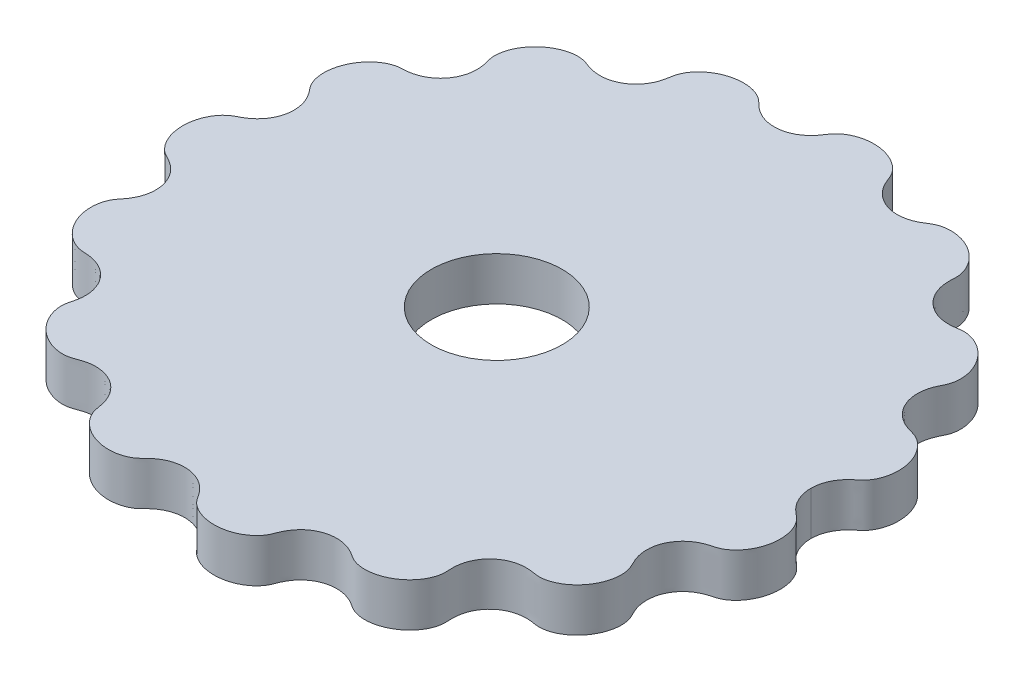
SolidWorks part; units mm, degrees
ref_plane "Front Plane" through (0, 0, 0) normal (0, 0, 1) x (1, 0, 0)
ref_plane "Top Plane" through (0, 0, 0) normal (0, 1, 0) x (1, 0, 0)
ref_plane "Right Plane" through (0, 0, 0) normal (1, 0, 0) x (0, 0, -1)
sketch "Sketch1" plane through (0, 0, 0) normal (0, 1, 0) x (1, 0, 0)
  circle A0 centre (0, 0) radius 50.8 construction
  circle A1 centre (50.8, 0) radius 5.08
  circle A2 centre (46.9331, -19.4403) radius 5.08
  circle A3 centre (35.921, -35.921) radius 5.08
  circle A4 centre (19.4403, -46.9331) radius 5.08
  circle A5 centre (0, -50.8) radius 5.08
  circle A6 centre (-19.4403, -46.9331) radius 5.08
  circle A7 centre (-35.921, -35.921) radius 5.08
  circle A8 centre (-46.9331, -19.4403) radius 5.08
  circle A9 centre (-50.8, 0) radius 5.08
  circle A10 centre (-46.9331, 19.4403) radius 5.08
  circle A11 centre (-35.921, 35.921) radius 5.08
  circle A12 centre (-19.4403, 46.9331) radius 5.08
  circle A13 centre (0, 50.8) radius 5.08
  circle A14 centre (19.4403, 46.9331) radius 5.08
  circle A15 centre (35.921, 35.921) radius 5.08
  circle A16 centre (46.9331, 19.4403) radius 5.08
  point P5 (0, 0)
  point P38 (0, 0)
  dimension "D2" = 10.16
  dimension "D3" = 101.6
  dimension "D1" = 16
sketch "Sketch7" plane through (0, 0, 0) normal (0, 1, 0) x (1, 0, 0)
  line L0 (45.72, 0) -> (-45.72, 0) construction
  circle A0 centre (0, 0) radius 9.525
  spline S0 degree 4 poles (41.7828, 21.3416) (41.6877, 21.0354) (41.5541, 20.4589) (41.4817, 19.5946) (41.6319, 18.466) (41.9776, 17.4811) (42.4848, 16.6203) (43.1091, 15.902) (43.7743, 15.3578) (44.4718, 14.9491) (45.1642, 14.6592) (45.8268, 14.4665) (46.5456, 14.2893) (47.2514, 13.9249) (47.9146, 13.4096) (48.5159, 12.7518) (49.1405, 11.8267) (49.6007, 10.7687) (49.8728, 9.6056) (49.9193, 8.478) (49.8408, 7.6516) (49.6901, 6.9642) (49.5102, 6.4154) (49.2842, 5.9083) (49.0159, 5.4485) (48.7039, 5.0361) (48.3472, 4.6843) (47.9659, 4.386) (47.6077, 4.0839) (47.2427, 3.7363) (46.8855, 3.332) (46.5599, 2.8811) (46.3097, 2.4416) (46.1346, 2.0602) (46.0214, 1.7622) (45.9477, 1.5375) (45.8879, 1.3243) (45.8399, 1.1244) (45.7998, 0.9214) (45.7677, 0.7202) (45.7435, 0.5098) (45.7274, 0.3215) (45.7201, 0.093) (45.7193, -0.0301) (45.7237, -0.2191) (45.7347, -0.4227) (45.7566, -0.6387) (45.8027, -0.9544) (45.8678, -1.2569) (45.9509, -1.5555) (46.0513, -1.8439) (46.1426, -2.0726) (46.2448, -2.2971) (46.3576, -2.5177) (46.4921, -2.7533) (46.6515, -3.0019) (46.8889, -3.3295) (47.1748, -3.6638) (47.4944, -3.9813) (47.8426, -4.2835) (48.1438, -4.5247) (48.4598, -4.7892) (48.7604, -5.1083) (49.0364, -5.4828) (49.2825, -5.909) (49.5155, -6.4255) (49.714, -7.0358) (49.8644, -7.7856) (49.9209, -8.6713) (49.8533, -9.5885) (49.6516, -10.518) (49.3412, -11.3668) (48.9446, -12.1262) (48.4522, -12.8268) (47.8657, -13.4526) (47.2676, -13.9089) (46.6958, -14.2089) (46.1258, -14.398) (45.5852, -14.5294) (44.9666, -14.7315) (44.2565, -15.0606) (43.5536, -15.5189) (42.899, -16.1145) (42.3292, -16.8533) (41.8937, -17.6927) (41.6203, -18.5741) (41.5051, -19.4792) (41.5386, -20.2622) (41.6529, -20.9023) (41.8006, -21.4183) (41.9452, -21.814) (42.1035, -22.1727) (42.2646, -22.4973) (42.4167, -22.7936) (42.5437, -23.0698) (42.697, -23.4938) (42.8228, -24.0797) (42.8641, -24.8222) (42.768, -25.7034) (42.4887, -26.7749) (42.0102, -27.8013) (41.345, -28.748) (40.5398, -29.5398) (39.8341, -30.0647) (39.1704, -30.4316) (38.5808, -30.6714) (38.04, -30.8244) (37.5594, -30.9071) (37.0754, -30.9359) (36.596, -30.895) (36.1253, -30.8116) (35.6524, -30.7507) (35.1502, -30.7185) (34.6202, -30.7308) (34.092, -30.7942) (33.571, -30.9112) (32.9559, -31.113) (32.2833, -31.4319) (31.5714, -31.9189) (30.8711, -32.6214) (30.3253, -33.4205) (29.9607, -34.2423) (29.751, -35.0481) (29.6728, -35.7135) (29.6616, -36.2359) (29.6773, -36.6738) (29.6986, -37.0273) (29.703, -37.4115) (29.6613, -37.8237) (29.5421, -38.3738) (29.3091, -39.0008) (28.9558, -39.6555) (28.3033, -40.5395) (27.4938, -41.3009) (26.5186, -41.9353) (25.4439, -42.3769) (24.5885, -42.5982) (23.71, -42.704) (22.9482, -42.686) (22.2698, -42.5723) (21.7118, -42.3914) (21.315, -42.2087) (20.9653, -41.9934) (20.6442, -41.7815) (20.2521, -41.543) (19.7793, -41.2964) (19.1439, -41.0412) (18.3354, -40.8422) (17.4171, -40.7711) (16.434, -40.8806) (15.5085, -41.1648) (14.6572, -41.6086) (13.9228, -42.1757) (13.3948, -42.751) (13.028, -43.2793) (12.7818, -43.7128) (12.6237, -44.0407) (12.4591, -44.4172) (12.3047, -44.8455) (12.0692, -45.3922) (11.6517, -45.9954) (11.094, -46.5595) (10.4034, -47.0611) (9.4514, -47.5695) (8.1925, -47.9781) (6.8691, -48.1066) (5.5546, -47.9462) (4.5084, -47.6213) (3.7265, -47.2501) (3.0557, -46.7811) (2.5196, -46.2235) (2.1335, -45.5991) (1.7387, -45.0258) (1.2259, -44.4389) (0.5606, -43.873) (-0.2214, -43.4057) (-1.1112, -43.0704) (-2.0596, -42.8988) (-3.0043, -42.9012) (-3.9242, -43.0698) (-4.7447, -43.3742) (-5.45, -43.7687) (-6.0504, -44.2213) (-6.5535, -44.6967) (-7.0661, -45.2369) (-7.7366, -45.6749) (-8.5217, -45.997) (-9.4012, -46.1925) (-10.5272, -46.2712) (-11.8972, -46.1123) (-13.1788, -45.661) (-14.3042, -44.9581) (-15.0295, -44.2955) (-15.4403, -43.8222) (-15.7542, -43.3701) (-15.9854, -42.9557) (-16.1672, -42.5257) (-16.2916, -42.0835) (-16.3602, -41.6378) (-16.4318, -41.201) (-16.5419, -40.7021) (-16.7135, -40.1493) (-16.994, -39.5043) (-17.4394, -38.7852) (-18.0402, -38.1012) (-18.8039, -37.5012) (-19.6799, -37.0449) (-20.6096, -36.7624) (-21.5079, -36.6612) (-22.3439, -36.7044) (-23.0054, -36.8321) (-23.5091, -36.9809) (-23.9227, -37.1304) (-24.2528, -37.2599) (-24.6165, -37.386) (-25.0218, -37.4775) (-25.5835, -37.5383) (-26.2546, -37.514) (-26.9898, -37.3829) (-28.0375, -37.0377) (-29.2307, -36.3867) (-30.2543, -35.4798) (-31.0464, -34.3719) (-31.5233, -33.3526) (-31.7439, -32.6266) (-31.8489, -31.9497) (-31.8537, -31.3655) (-31.8069, -30.9328) (-31.7138, -30.5342) (-31.6113, -30.1645) (-31.5042, -29.7205) (-31.413, -29.1982) (-31.3618, -28.5192) (-31.4147, -27.6932) (-31.6211, -26.8) (-32.0182, -25.8969) (-32.5655, -25.0985) (-33.2452, -24.4168) (-34.0098, -23.8834) (-34.7213, -23.5509) (-35.339, -23.3594) (-35.8294, -23.2554) (-36.1919, -23.2037) (-36.6026, -23.1617) (-37.059, -23.1457) (-37.6539, -23.0966) (-38.3607, -22.8907) (-39.0742, -22.5374) (-39.77, -22.0364) (-40.5537, -21.2875) (-41.3351, -20.2168) (-41.8688, -18.9991) (-42.1255, -17.7015) (-42.1433, -16.6109) (-42.0363, -15.7552) (-41.8023, -14.9745) (-41.4457, -14.291) (-40.976, -13.7302) (-40.5508, -13.1832) (-40.1492, -12.5194) (-39.8116, -11.7187) (-39.6021, -10.8369) (-39.5488, -9.8916) (-39.669, -8.9318) (-39.9579, -8.0204) (-40.4076, -7.1756) (-40.9716, -6.4617) (-41.5285, -5.9525) (-42.0303, -5.595) (-42.4275, -5.3578) (-42.7375, -5.1916) (-43.0379, -5.0401) (-43.321, -4.8882) (-43.7217, -4.6273) (-44.1973, -4.2074) (-44.6713, -3.6237) (-45.1006, -2.8706) (-45.5075, -1.8491) (-45.7775, -0.522) (-45.7428, 1.0312) (-45.3293, 2.4487) (-44.7945, 3.4311) (-44.337, 4.0254) (-44.0051, 4.3768) (-43.6551, 4.6727) (-43.292, 4.9094) (-42.8421, 5.1383) (-42.3334, 5.401) (-41.7729, 5.7601) (-41.1532, 6.281) (-40.5747, 6.9382) (-40.0873, 7.7315) (-39.7369, 8.6511) (-39.5619, 9.6313) (-39.5711, 10.607) (-39.7455, 11.4988) (-40.0404, 12.287) (-40.3641, 12.8819) (-40.6603, 13.3187) (-40.93, 13.668) (-41.1551, 13.9424) (-41.3902, 14.2481) (-41.6063, 14.6044) (-41.8422, 15.1201) (-42.031, 15.7675) (-42.1371, 16.5098) (-42.1363, 17.6175) (-41.8908, 18.9447) (-41.3448, 20.213) (-40.5162, 21.3399) (-39.7576, 22.0421) (-39.2078, 22.4355) (-38.7051, 22.7151) (-38.2693, 22.9048) (-37.8329, 23.0404) (-37.4014, 23.1196) (-36.9831, 23.1458) (-36.5836, 23.1656) (-36.1327, 23.2073) (-35.6335, 23.2882) (-35.0072, 23.4498) (-34.2813, 23.7424) (-33.5245, 24.1953) (-32.7976, 24.8352) (-32.2068, 25.5879) (-31.7606, 26.4376) (-31.4792, 27.331) (-31.3635, 28.2054) (-31.3863, 29.0412) (-31.4947, 29.6981) (-31.6186, 30.1887) (-31.7204, 30.5657) (-31.7826, 30.8337) (-31.8505, 31.2648) (-31.8625, 31.8634) (-31.7598, 32.587) (-31.5014, 33.4078) (-31.0323, 34.3906) (-30.2573, 35.468) (-29.2659, 36.3541) (-28.1141, 37.0013) (-27.088, 37.3569) (-26.2453, 37.523) (-25.434, 37.5456) (-24.675, 37.4255) (-23.997, 37.1573) (-23.3499, 36.9185) (-22.5991, 36.7383) (-21.7385, 36.6578) (-20.8392, 36.7228) (-19.9253, 36.9541) (-19.0472, 37.3546) (-18.2636, 37.9025) (-17.5893, 38.5866) (-17.0752, 39.3423) (-16.755, 40.0305) (-16.5659, 40.6197) (-16.4397, 41.1507) (-16.3573, 41.6572) (-16.26, 42.3087) (-15.962, 43.0543) (-15.5133, 43.7588) (-14.9289, 44.4055) (-14.0825, 45.114) (-12.8873, 45.7941) (-11.5846, 46.1836) (-10.2568, 46.272) (-9.2873, 46.1614) (-8.7022, 46.0294) (-8.1809, 45.8529) (-7.7255, 45.6444) (-7.3091, 45.3928) (-6.9412, 45.0972) (-6.6224, 44.773) (-6.3099, 44.4662) (-5.9526, 44.1515) (-5.5419, 43.8428) (-5.091, 43.5656) (-4.6007, 43.329) (-3.9784, 43.1008) (-3.238, 42.933) (-2.3608, 42.8777) (-1.3623, 43.0053) (-0.4305, 43.3076) (0.3718, 43.7445) (1.0377, 44.2658) (1.5092, 44.7569) (1.837, 45.1739) (2.088, 45.5386) (2.2802, 45.8377) (2.4965, 46.1579) (2.7663, 46.4768) (3.0946, 46.7829) (3.4794, 47.0696) (3.9555, 47.3561) (4.5291, 47.6214) (5.4715, 47.9304) (6.7893, 48.1076) (8.1418, 47.991) (9.4509, 47.5732) (10.4339, 47.0458) (11.1485, 46.5141) (11.7277, 45.9067) (12.1597, 45.2408) (12.4223, 44.504) (12.7219, 43.7892) (13.1497, 43.0628) (13.7216, 42.3719) (14.4157, 41.7738) (15.2117, 41.2995) (16.0702, 40.9746) (16.983, 40.8025) (17.8917, 40.7909) (18.7379, 40.9242) (19.511, 41.1732) (20.1754, 41.4903) (20.7471, 41.844) (21.3419, 42.2475) (22.0563, 42.5293) (22.8662, 42.6852) (23.7515, 42.7039) (24.8493, 42.5641) (26.1339, 42.1532) (27.2837, 41.4825) (28.2447, 40.6011) (28.9001, 39.7411) (29.3199, 38.9962) (29.5954, 38.2361) (29.7212, 37.4818) (29.6887, 36.8535) (29.6621, 36.3625) (29.6696, 35.823) (29.7257, 35.2082) (29.8882, 34.4621) (30.218, 33.6285) (30.7107, 32.829) (31.3534, 32.1126) (32.1105, 31.528) (32.9677, 31.0876) (33.8471, 30.8224) (34.6036, 30.7239) (35.2255, 30.7211) (35.7717, 30.7627) (36.2815, 30.8374) (36.9328, 30.9524) (37.7381, 30.907) (38.5518, 30.7013) (39.3526, 30.3476) (40.2945, 29.762) (41.1367, 28.9979) (41.8647, 28.0459) (42.4447, 26.8746) (42.7562, 25.8409) (42.8645, 24.9056) (42.8206, 24.1058) (42.7043, 23.5329) (42.5689, 23.1192) (42.3954, 22.7479) (42.2174, 22.4073) (42.0522, 22.0606) (41.9041, 21.7072) (41.7474, 21.2554) (41.5943, 20.649) (41.5001, 19.8626) (41.5501, 18.9284) (41.7844, 17.973) (42.194, 17.0726) (42.7458, 16.2844) (43.3781, 15.6612) (44.0387, 15.1921) (44.6289, 14.8828) (45.1286, 14.6816) (45.5872, 14.5353) (45.9966, 14.4268) (46.4174, 14.3103) (46.8324, 14.1376) (47.2336, 13.9105) (47.6175, 13.6346) (48.0316, 13.2717) (48.4577, 12.8088) (48.8968, 12.204) (49.3083, 11.443) (49.5917, 10.6946) (49.7696, 9.9824) (49.8623, 9.3599) (49.8995, 8.8359) (49.8955, 8.2844) (49.8376, 7.6605) (49.7313, 7.1266) (49.5999, 6.6843) (49.4752, 6.3548) (49.3998, 6.1752) (49.3174, 5.9981) (49.2284, 5.8248) (49.1466, 5.6794) (49.0624, 5.5434) (48.9893, 5.4317) (48.9431, 5.3651) (48.8825, 5.282) (48.7864, 5.1562) (48.6684, 5.0143) (48.506, 4.8413) (48.2587, 4.6173) (47.9722, 4.3887) (47.6611, 4.1305) (47.3391, 3.8308) (46.9423, 3.4059) (46.512, 2.8312) (46.1043, 2.075) (45.8063, 1.1379) (45.687, 0.1795) (45.742, -0.7727) (45.9614, -1.6871) (46.306, -2.4748) (46.7236, -3.131) (47.1363, -3.6248) (47.4973, -3.9838) (47.8417, -4.2831) (48.1568, -4.5347) (48.4781, -4.806) (48.7753, -5.1273) (49.0422, -5.4935) (49.2765, -5.8996) (49.505, -6.4) (49.7046, -6.9998) (49.9045, -7.9629) (49.9365, -9.341) (49.6587, -10.6765) (49.1039, -11.8907) (48.4688, -12.8036) (47.9714, -13.3447) (47.4423, -13.7809) (46.9321, -14.0869) (46.5394, -14.2637) (46.1675, -14.3819) (45.8287, -14.4696) (45.5763, -14.5419) (45.4093, -14.594) (45.3261, -14.6211) knots 0 0 0 0 0 0.003326 0.006122 0.008927 0.011729 0.01408 0.016425 0.018755 0.0206 0.022444 0.024183 0.025921 0.028253 0.030605 0.032863 0.035121 0.0398 0.042485 0.04517 0.04678 0.048389 0.049771 0.051153 0.052528 0.053903 0.055118 0.056333 0.057549 0.058764 0.060343 0.061922 0.063308 0.064 0.064693 0.065227 0.065761 0.066295 0.066829 0.067363 0.067898 0.068432 0.068966 0.069299 0.069632 0.070299 0.070966 0.071632 0.072898 0.073532 0.074165 0.074807 0.075449 0.076091 0.076733 0.077622 0.07851 0.080287 0.081289 0.08229 0.083291 0.084293 0.085559 0.086825 0.088107 0.089389 0.091429 0.093469 0.096019 0.098568 0.100937 0.103305 0.105367 0.10743 0.109796 0.112168 0.11313 0.114091 0.116015 0.11794 0.119866 0.122189 0.124687 0.127076 0.129494 0.13195 0.134211 0.136496 0.137588 0.13868 0.139772 0.140865 0.141652 0.14244 0.143228 0.144016 0.146324 0.148631 0.150903 0.153175 0.157773 0.1603 0.162827 0.164849 0.16687 0.168143 0.169417 0.170669 0.171922 0.173158 0.174394 0.175629 0.176865 0.178375 0.179884 0.18114 0.182395 0.185083 0.187579 0.190035 0.192629 0.195066 0.196855 0.198643 0.199562 0.200481 0.2014 0.202319 0.203544 0.204768 0.207228 0.209231 0.211233 0.216135 0.218674 0.221212 0.223244 0.225275 0.227827 0.229088 0.230349 0.231347 0.232346 0.233344 0.234342 0.236107 0.237871 0.240431 0.242948 0.245608 0.248072 0.250416 0.252856 0.255188 0.256132 0.257077 0.258022 0.258967 0.260387 0.261808 0.264173 0.266525 0.268577 0.270629 0.275341 0.28016 0.282214 0.284267 0.286675 0.289103 0.290661 0.292219 0.294273 0.296327 0.298714 0.301249 0.303673 0.30614 0.308659 0.310994 0.313327 0.315173 0.31702 0.318766 0.320513 0.322872 0.325249 0.327532 0.329815 0.334546 0.339451 0.341464 0.343478 0.344709 0.345939 0.347166 0.348393 0.349541 0.35069 0.351839 0.352987 0.354837 0.356686 0.359114 0.36173 0.364229 0.366703 0.369305 0.371753 0.373555 0.375357 0.376277 0.377196 0.378116 0.379036 0.380266 0.381496 0.383965 0.385975 0.387986 0.392908 0.397962 0.399985 0.402008 0.40455 0.405805 0.407061 0.408057 0.409052 0.410047 0.411042 0.412794 0.414545 0.417095 0.419597 0.422252 0.42472 0.427079 0.429532 0.431875 0.432826 0.433776 0.434727 0.435677 0.4371 0.438523 0.440897 0.44326 0.44532 0.447381 0.452113 0.456913 0.458958 0.461003 0.463401 0.46582 0.467374 0.468928 0.47097 0.473013 0.475389 0.477913 0.480321 0.482785 0.485369 0.487778 0.490195 0.492177 0.493168 0.494159 0.494992 0.495825 0.496658 0.497492 0.499943 0.502376 0.504415 0.506453 0.511318 0.516326 0.520334 0.521593 0.522852 0.524095 0.525339 0.526337 0.527335 0.529332 0.531277 0.533223 0.535709 0.538378 0.54088 0.543372 0.545982 0.548442 0.550256 0.552069 0.55299 0.553911 0.554832 0.555753 0.556988 0.558223 0.560702 0.562721 0.564739 0.569681 0.574601 0.57687 0.579138 0.580368 0.581598 0.582829 0.584061 0.585099 0.586136 0.587174 0.588211 0.589794 0.591376 0.593871 0.596304 0.598895 0.601368 0.603741 0.606209 0.608563 0.610474 0.612385 0.613098 0.613812 0.614525 0.615238 0.61762 0.619995 0.622064 0.624134 0.628886 0.633666 0.635703 0.637739 0.640126 0.642537 0.644087 0.645638 0.647668 0.649699 0.652064 0.654577 0.65697 0.65943 0.662021 0.664443 0.666878 0.668867 0.669862 0.670857 0.67253 0.674203 0.676666 0.679109 0.681157 0.683204 0.688091 0.693269 0.695085 0.696901 0.698191 0.699481 0.700785 0.702089 0.703225 0.704361 0.705498 0.706634 0.70816 0.709685 0.710979 0.712273 0.715026 0.717532 0.720041 0.722659 0.72513 0.726956 0.728781 0.729704 0.730626 0.731548 0.732471 0.73371 0.734949 0.736194 0.73744 0.739466 0.741492 0.746454 0.75113 0.753386 0.755643 0.757994 0.760324 0.76206 0.763797 0.766082 0.768368 0.770759 0.773067 0.775538 0.777935 0.78023 0.782657 0.784922 0.786777 0.788632 0.790267 0.791902 0.794211 0.796528 0.798787 0.801045 0.805658 0.810418 0.812447 0.814475 0.81685 0.819251 0.820796 0.822341 0.823352 0.824363 0.826384 0.828739 0.831241 0.833618 0.836075 0.838673 0.841108 0.84356 0.845556 0.846554 0.847552 0.849232 0.850913 0.853386 0.855842 0.857898 0.859955 0.864864 0.867551 0.870238 0.87346 0.876006 0.87726 0.878514 0.879512 0.880509 0.881506 0.882504 0.883493 0.884483 0.886463 0.88898 0.891675 0.894132 0.896608 0.899187 0.901601 0.903293 0.904984 0.906084 0.907183 0.908282 0.909381 0.910607 0.911833 0.913055 0.914277 0.916312 0.918347 0.920786 0.923226 0.924587 0.925948 0.927309 0.92867 0.930302 0.932439 0.932945 0.93345 0.933956 0.934461 0.934967 0.935472 0.935725 0.935978 0.936361 0.936552 0.936743 0.937509 0.938275 0.93904 0.940181 0.941322 0.942463 0.943603 0.946205 0.948751 0.951324 0.953747 0.956169 0.958595 0.961029 0.962621 0.964212 0.965259 0.966305 0.967351 0.968397 0.969615 0.970833 0.972043 0.973253 0.975315 0.977377 0.982218 0.98745 0.989285 0.99112 0.993728 0.995049 0.996369 0.997277 0.998184 0.999092 1 1 1 1 1 construction
  spline S1 degree 4 poles (45.72, 0) (45.72, -0.0279) (45.7205, -0.0841) (45.7237, -0.2191) (45.7347, -0.4227) (45.7566, -0.6387) (45.8027, -0.9544) (45.8678, -1.2569) (45.9509, -1.5555) (46.0513, -1.8439) (46.1426, -2.0726) (46.2448, -2.2971) (46.3576, -2.5177) (46.4921, -2.7533) (46.6515, -3.0019) (46.8889, -3.3295) (47.1748, -3.6638) (47.4944, -3.9813) (47.8426, -4.2835) (48.1438, -4.5247) (48.4598, -4.7892) (48.7604, -5.1083) (49.0364, -5.4828) (49.2825, -5.909) (49.5155, -6.4255) (49.714, -7.0358) (49.8644, -7.7856) (49.9209, -8.6713) (49.8533, -9.5885) (49.6516, -10.518) (49.3412, -11.3668) (48.9446, -12.1262) (48.4522, -12.8268) (47.8657, -13.4526) (47.2676, -13.9089) (46.6958, -14.2089) (46.1258, -14.398) (45.5852, -14.5294) (44.9666, -14.7315) (44.2565, -15.0606) (43.5536, -15.5189) (42.899, -16.1145) (42.3292, -16.8533) (41.8937, -17.6927) (41.6203, -18.5741) (41.5051, -19.4792) (41.5386, -20.2622) (41.6529, -20.9023) (41.8006, -21.4183) (41.9452, -21.814) (42.1035, -22.1727) (42.2646, -22.4973) (42.4167, -22.7936) (42.5437, -23.0698) (42.697, -23.4938) (42.8228, -24.0797) (42.8641, -24.8222) (42.768, -25.7034) (42.4887, -26.7749) (42.0102, -27.8013) (41.345, -28.748) (40.5398, -29.5398) (39.8341, -30.0647) (39.1704, -30.4316) (38.5808, -30.6714) (38.04, -30.8244) (37.5594, -30.9071) (37.0754, -30.9359) (36.596, -30.895) (36.1253, -30.8116) (35.6524, -30.7507) (35.1502, -30.7185) (34.6202, -30.7308) (34.092, -30.7942) (33.571, -30.9112) (32.9559, -31.113) (32.2833, -31.4319) (31.5714, -31.9189) (30.8711, -32.6214) (30.3253, -33.4205) (29.9607, -34.2423) (29.751, -35.0481) (29.6728, -35.7135) (29.6616, -36.2359) (29.6773, -36.6738) (29.6986, -37.0273) (29.703, -37.4115) (29.6613, -37.8237) (29.5421, -38.3738) (29.3091, -39.0008) (28.9558, -39.6555) (28.3033, -40.5395) (27.4938, -41.3009) (26.5186, -41.9353) (25.4439, -42.3769) (24.5885, -42.5982) (23.71, -42.704) (22.9482, -42.686) (22.2698, -42.5723) (21.7118, -42.3914) (21.315, -42.2087) (20.9653, -41.9934) (20.6442, -41.7815) (20.2521, -41.543) (19.7793, -41.2964) (19.1439, -41.0412) (18.3354, -40.8422) (17.4171, -40.7711) (16.434, -40.8806) (15.5085, -41.1648) (14.6572, -41.6086) (13.9228, -42.1757) (13.3948, -42.751) (13.028, -43.2793) (12.7818, -43.7128) (12.6237, -44.0407) (12.4591, -44.4172) (12.3047, -44.8455) (12.0692, -45.3922) (11.6517, -45.9954) (11.094, -46.5595) (10.4034, -47.0611) (9.4514, -47.5695) (8.1925, -47.9781) (6.8691, -48.1066) (5.5546, -47.9462) (4.5084, -47.6213) (3.7265, -47.2501) (3.0557, -46.7811) (2.5196, -46.2235) (2.1335, -45.5991) (1.7387, -45.0258) (1.2259, -44.4389) (0.5606, -43.873) (-0.2214, -43.4057) (-1.1112, -43.0704) (-2.0596, -42.8988) (-3.0043, -42.9012) (-3.9242, -43.0698) (-4.7447, -43.3742) (-5.45, -43.7687) (-6.0504, -44.2213) (-6.5535, -44.6967) (-7.0661, -45.2369) (-7.7366, -45.6749) (-8.5217, -45.997) (-9.4012, -46.1925) (-10.5272, -46.2712) (-11.8972, -46.1123) (-13.1788, -45.661) (-14.3042, -44.9581) (-15.0295, -44.2955) (-15.4403, -43.8222) (-15.7542, -43.3701) (-15.9854, -42.9557) (-16.1672, -42.5257) (-16.2916, -42.0835) (-16.3602, -41.6378) (-16.4318, -41.201) (-16.5419, -40.7021) (-16.7135, -40.1493) (-16.994, -39.5043) (-17.4394, -38.7852) (-18.0402, -38.1012) (-18.8039, -37.5012) (-19.6799, -37.0449) (-20.6096, -36.7624) (-21.5079, -36.6612) (-22.3439, -36.7044) (-23.0054, -36.8321) (-23.5091, -36.9809) (-23.9227, -37.1304) (-24.2528, -37.2599) (-24.6165, -37.386) (-25.0218, -37.4775) (-25.5835, -37.5383) (-26.2546, -37.514) (-26.9898, -37.3829) (-28.0375, -37.0377) (-29.2307, -36.3867) (-30.2543, -35.4798) (-31.0464, -34.3719) (-31.5233, -33.3526) (-31.7439, -32.6266) (-31.8489, -31.9497) (-31.8537, -31.3655) (-31.8069, -30.9328) (-31.7138, -30.5342) (-31.6113, -30.1645) (-31.5042, -29.7205) (-31.413, -29.1982) (-31.3618, -28.5192) (-31.4147, -27.6932) (-31.6211, -26.8) (-32.0182, -25.8969) (-32.5655, -25.0985) (-33.2452, -24.4168) (-34.0098, -23.8834) (-34.7213, -23.5509) (-35.339, -23.3594) (-35.8294, -23.2554) (-36.1919, -23.2037) (-36.6026, -23.1617) (-37.059, -23.1457) (-37.6539, -23.0966) (-38.3607, -22.8907) (-39.0742, -22.5374) (-39.77, -22.0364) (-40.5537, -21.2875) (-41.3351, -20.2168) (-41.8688, -18.9991) (-42.1255, -17.7015) (-42.1433, -16.6109) (-42.0363, -15.7552) (-41.8023, -14.9745) (-41.4457, -14.291) (-40.976, -13.7302) (-40.5508, -13.1832) (-40.1492, -12.5194) (-39.8116, -11.7187) (-39.6021, -10.8369) (-39.5488, -9.8916) (-39.669, -8.9318) (-39.9579, -8.0204) (-40.4076, -7.1756) (-40.9716, -6.4617) (-41.5285, -5.9525) (-42.0303, -5.595) (-42.4275, -5.3578) (-42.7375, -5.1916) (-43.0379, -5.0401) (-43.321, -4.8882) (-43.7217, -4.6273) (-44.1973, -4.2074) (-44.6713, -3.6237) (-45.1006, -2.8706) (-45.4948, -1.881) (-45.6666, -1.0659) (-45.72, -0.4347) (-45.72, 0) knots 0.068966 0.068966 0.068966 0.068966 0.068966 0.069299 0.069632 0.070299 0.070966 0.071632 0.072898 0.073532 0.074165 0.074807 0.075449 0.076091 0.076733 0.077622 0.07851 0.080287 0.081289 0.08229 0.083291 0.084293 0.085559 0.086825 0.088107 0.089389 0.091429 0.093469 0.096019 0.098568 0.100937 0.103305 0.105367 0.10743 0.109796 0.112168 0.11313 0.114091 0.116015 0.11794 0.119866 0.122189 0.124687 0.127076 0.129494 0.13195 0.134211 0.136496 0.137588 0.13868 0.139772 0.140865 0.141652 0.14244 0.143228 0.144016 0.146324 0.148631 0.150903 0.153175 0.157773 0.1603 0.162827 0.164849 0.16687 0.168143 0.169417 0.170669 0.171922 0.173158 0.174394 0.175629 0.176865 0.178375 0.179884 0.18114 0.182395 0.185083 0.187579 0.190035 0.192629 0.195066 0.196855 0.198643 0.199562 0.200481 0.2014 0.202319 0.203544 0.204768 0.207228 0.209231 0.211233 0.216135 0.218674 0.221212 0.223244 0.225275 0.227827 0.229088 0.230349 0.231347 0.232346 0.233344 0.234342 0.236107 0.237871 0.240431 0.242948 0.245608 0.248072 0.250416 0.252856 0.255188 0.256132 0.257077 0.258022 0.258967 0.260387 0.261808 0.264173 0.266525 0.268577 0.270629 0.275341 0.28016 0.282214 0.284267 0.286675 0.289103 0.290661 0.292219 0.294273 0.296327 0.298714 0.301249 0.303673 0.30614 0.308659 0.310994 0.313327 0.315173 0.31702 0.318766 0.320513 0.322872 0.325249 0.327532 0.329815 0.334546 0.339451 0.341464 0.343478 0.344709 0.345939 0.347166 0.348393 0.349541 0.35069 0.351839 0.352987 0.354837 0.356686 0.359114 0.36173 0.364229 0.366703 0.369305 0.371753 0.373555 0.375357 0.376277 0.377196 0.378116 0.379036 0.380266 0.381496 0.383965 0.385975 0.387986 0.392908 0.397962 0.399985 0.402008 0.40455 0.405805 0.407061 0.408057 0.409052 0.410047 0.411042 0.412794 0.414545 0.417095 0.419597 0.422252 0.42472 0.427079 0.429532 0.431875 0.432826 0.433776 0.434727 0.435677 0.4371 0.438523 0.440897 0.44326 0.44532 0.447381 0.452113 0.456913 0.458958 0.461003 0.463401 0.46582 0.467374 0.468928 0.47097 0.473013 0.475389 0.477913 0.480321 0.482785 0.485369 0.487778 0.490195 0.492177 0.493168 0.494159 0.494992 0.495825 0.496658 0.497492 0.499943 0.502376 0.504415 0.506453 0.510963 0.510963 0.510963 0.510963 0.510963
  spline S2 degree 4 poles (45.72, 0) (45.72, 0.0279) (45.7205, 0.0841) (45.7237, 0.2191) (45.7347, 0.4227) (45.7566, 0.6387) (45.8027, 0.9544) (45.8678, 1.2569) (45.9509, 1.5555) (46.0513, 1.8439) (46.1426, 2.0726) (46.2448, 2.2971) (46.3576, 2.5177) (46.4921, 2.7533) (46.6515, 3.0019) (46.8889, 3.3295) (47.1748, 3.6638) (47.4944, 3.9813) (47.8426, 4.2835) (48.1438, 4.5247) (48.4598, 4.7892) (48.7604, 5.1083) (49.0364, 5.4828) (49.2825, 5.909) (49.5155, 6.4255) (49.714, 7.0358) (49.8644, 7.7856) (49.9209, 8.6713) (49.8533, 9.5885) (49.6516, 10.518) (49.3412, 11.3668) (48.9446, 12.1262) (48.4522, 12.8268) (47.8657, 13.4526) (47.2676, 13.9089) (46.6958, 14.2089) (46.1258, 14.398) (45.5852, 14.5294) (44.9666, 14.7315) (44.2565, 15.0606) (43.5536, 15.5189) (42.899, 16.1145) (42.3292, 16.8533) (41.8937, 17.6927) (41.6203, 18.5741) (41.5051, 19.4792) (41.5386, 20.2622) (41.6529, 20.9023) (41.8006, 21.4183) (41.9452, 21.814) (42.1035, 22.1727) (42.2646, 22.4973) (42.4167, 22.7936) (42.5437, 23.0698) (42.697, 23.4938) (42.8228, 24.0797) (42.8641, 24.8222) (42.768, 25.7034) (42.4887, 26.7749) (42.0102, 27.8013) (41.345, 28.748) (40.5398, 29.5398) (39.8341, 30.0647) (39.1704, 30.4316) (38.5808, 30.6714) (38.04, 30.8244) (37.5594, 30.9071) (37.0754, 30.9359) (36.596, 30.895) (36.1253, 30.8116) (35.6524, 30.7507) (35.1502, 30.7185) (34.6202, 30.7308) (34.092, 30.7942) (33.571, 30.9112) (32.9559, 31.113) (32.2833, 31.4319) (31.5714, 31.9189) (30.8711, 32.6214) (30.3253, 33.4205) (29.9607, 34.2423) (29.751, 35.0481) (29.6728, 35.7135) (29.6616, 36.2359) (29.6773, 36.6738) (29.6986, 37.0273) (29.703, 37.4115) (29.6613, 37.8237) (29.5421, 38.3738) (29.3091, 39.0008) (28.9558, 39.6555) (28.3033, 40.5395) (27.4938, 41.3009) (26.5186, 41.9353) (25.4439, 42.3769) (24.5885, 42.5982) (23.71, 42.704) (22.9482, 42.686) (22.2698, 42.5723) (21.7118, 42.3914) (21.315, 42.2087) (20.9653, 41.9934) (20.6442, 41.7815) (20.2521, 41.543) (19.7793, 41.2964) (19.1439, 41.0412) (18.3354, 40.8422) (17.4171, 40.7711) (16.434, 40.8806) (15.5085, 41.1648) (14.6572, 41.6086) (13.9228, 42.1757) (13.3948, 42.751) (13.028, 43.2793) (12.7818, 43.7128) (12.6237, 44.0407) (12.4591, 44.4172) (12.3047, 44.8455) (12.0692, 45.3922) (11.6517, 45.9954) (11.094, 46.5595) (10.4034, 47.0611) (9.4514, 47.5695) (8.1925, 47.9781) (6.8691, 48.1066) (5.5546, 47.9462) (4.5084, 47.6213) (3.7265, 47.2501) (3.0557, 46.7811) (2.5196, 46.2235) (2.1335, 45.5991) (1.7387, 45.0258) (1.2259, 44.4389) (0.5606, 43.873) (-0.2214, 43.4057) (-1.1112, 43.0704) (-2.0596, 42.8988) (-3.0043, 42.9012) (-3.9242, 43.0698) (-4.7447, 43.3742) (-5.45, 43.7687) (-6.0504, 44.2213) (-6.5535, 44.6967) (-7.0661, 45.2369) (-7.7366, 45.6749) (-8.5217, 45.997) (-9.4012, 46.1925) (-10.5272, 46.2712) (-11.8972, 46.1123) (-13.1788, 45.661) (-14.3042, 44.9581) (-15.0295, 44.2955) (-15.4403, 43.8222) (-15.7542, 43.3701) (-15.9854, 42.9557) (-16.1672, 42.5257) (-16.2916, 42.0835) (-16.3602, 41.6378) (-16.4318, 41.201) (-16.5419, 40.7021) (-16.7135, 40.1493) (-16.994, 39.5043) (-17.4394, 38.7852) (-18.0402, 38.1012) (-18.8039, 37.5012) (-19.6799, 37.0449) (-20.6096, 36.7624) (-21.5079, 36.6612) (-22.3439, 36.7044) (-23.0054, 36.8321) (-23.5091, 36.9809) (-23.9227, 37.1304) (-24.2528, 37.2599) (-24.6165, 37.386) (-25.0218, 37.4775) (-25.5835, 37.5383) (-26.2546, 37.514) (-26.9898, 37.3829) (-28.0375, 37.0377) (-29.2307, 36.3867) (-30.2543, 35.4798) (-31.0464, 34.3719) (-31.5233, 33.3526) (-31.7439, 32.6266) (-31.8489, 31.9497) (-31.8537, 31.3655) (-31.8069, 30.9328) (-31.7138, 30.5342) (-31.6113, 30.1645) (-31.5042, 29.7205) (-31.413, 29.1982) (-31.3618, 28.5192) (-31.4147, 27.6932) (-31.6211, 26.8) (-32.0182, 25.8969) (-32.5655, 25.0985) (-33.2452, 24.4168) (-34.0098, 23.8834) (-34.7213, 23.5509) (-35.339, 23.3594) (-35.8294, 23.2554) (-36.1919, 23.2037) (-36.6026, 23.1617) (-37.059, 23.1457) (-37.6539, 23.0966) (-38.3607, 22.8907) (-39.0742, 22.5374) (-39.77, 22.0364) (-40.5537, 21.2875) (-41.3351, 20.2168) (-41.8688, 18.9991) (-42.1255, 17.7015) (-42.1433, 16.6109) (-42.0363, 15.7552) (-41.8023, 14.9745) (-41.4457, 14.291) (-40.976, 13.7302) (-40.5508, 13.1832) (-40.1492, 12.5194) (-39.8116, 11.7187) (-39.6021, 10.8369) (-39.5488, 9.8916) (-39.669, 8.9318) (-39.9579, 8.0204) (-40.4076, 7.1756) (-40.9716, 6.4617) (-41.5285, 5.9525) (-42.0303, 5.595) (-42.4275, 5.3578) (-42.7375, 5.1916) (-43.0379, 5.0401) (-43.321, 4.8882) (-43.7217, 4.6273) (-44.1973, 4.2074) (-44.6713, 3.6237) (-45.1006, 2.8706) (-45.4948, 1.881) (-45.6666, 1.0659) (-45.72, 0.4347) (-45.72, 0) knots 0.068966 0.068966 0.068966 0.068966 0.068966 0.069299 0.069632 0.070299 0.070966 0.071632 0.072898 0.073532 0.074165 0.074807 0.075449 0.076091 0.076733 0.077622 0.07851 0.080287 0.081289 0.08229 0.083291 0.084293 0.085559 0.086825 0.088107 0.089389 0.091429 0.093469 0.096019 0.098568 0.100937 0.103305 0.105367 0.10743 0.109796 0.112168 0.11313 0.114091 0.116015 0.11794 0.119866 0.122189 0.124687 0.127076 0.129494 0.13195 0.134211 0.136496 0.137588 0.13868 0.139772 0.140865 0.141652 0.14244 0.143228 0.144016 0.146324 0.148631 0.150903 0.153175 0.157773 0.1603 0.162827 0.164849 0.16687 0.168143 0.169417 0.170669 0.171922 0.173158 0.174394 0.175629 0.176865 0.178375 0.179884 0.18114 0.182395 0.185083 0.187579 0.190035 0.192629 0.195066 0.196855 0.198643 0.199562 0.200481 0.2014 0.202319 0.203544 0.204768 0.207228 0.209231 0.211233 0.216135 0.218674 0.221212 0.223244 0.225275 0.227827 0.229088 0.230349 0.231347 0.232346 0.233344 0.234342 0.236107 0.237871 0.240431 0.242948 0.245608 0.248072 0.250416 0.252856 0.255188 0.256132 0.257077 0.258022 0.258967 0.260387 0.261808 0.264173 0.266525 0.268577 0.270629 0.275341 0.28016 0.282214 0.284267 0.286675 0.289103 0.290661 0.292219 0.294273 0.296327 0.298714 0.301249 0.303673 0.30614 0.308659 0.310994 0.313327 0.315173 0.31702 0.318766 0.320513 0.322872 0.325249 0.327532 0.329815 0.334546 0.339451 0.341464 0.343478 0.344709 0.345939 0.347166 0.348393 0.349541 0.35069 0.351839 0.352987 0.354837 0.356686 0.359114 0.36173 0.364229 0.366703 0.369305 0.371753 0.373555 0.375357 0.376277 0.377196 0.378116 0.379036 0.380266 0.381496 0.383965 0.385975 0.387986 0.392908 0.397962 0.399985 0.402008 0.40455 0.405805 0.407061 0.408057 0.409052 0.410047 0.411042 0.412794 0.414545 0.417095 0.419597 0.422252 0.42472 0.427079 0.429532 0.431875 0.432826 0.433776 0.434727 0.435677 0.4371 0.438523 0.440897 0.44326 0.44532 0.447381 0.452113 0.456913 0.458958 0.461003 0.463401 0.46582 0.467374 0.468928 0.47097 0.473013 0.475389 0.477913 0.480321 0.482785 0.485369 0.487778 0.490195 0.492177 0.493168 0.494159 0.494992 0.495825 0.496658 0.497492 0.499943 0.502376 0.504415 0.506453 0.510963 0.510963 0.510963 0.510963 0.510963
  point P4 (0, 0)
  point P6 (-11.4329, 0)
  point P7 (0, 0)
  point P10 (0, -2.54)
  point P11 (-2.54, 0)
  point P12 (0, 0)
  dimension "D1" = 19.05
extrude "cycloid" add sketch "Sketch7" along normal blind 6.35
equation "\"outerring_dia\"= 4"
equation "\"D3@Sketch1\"=\"outerring_dia\""
equation "\"roller_dia\"=0.4"
equation "\"D2@Sketch1\"=\"roller_dia\""
equation "\"number_outer_rollers\"=16"
equation "\"D1@Sketch1\"=\"number_outer_rollers\""
